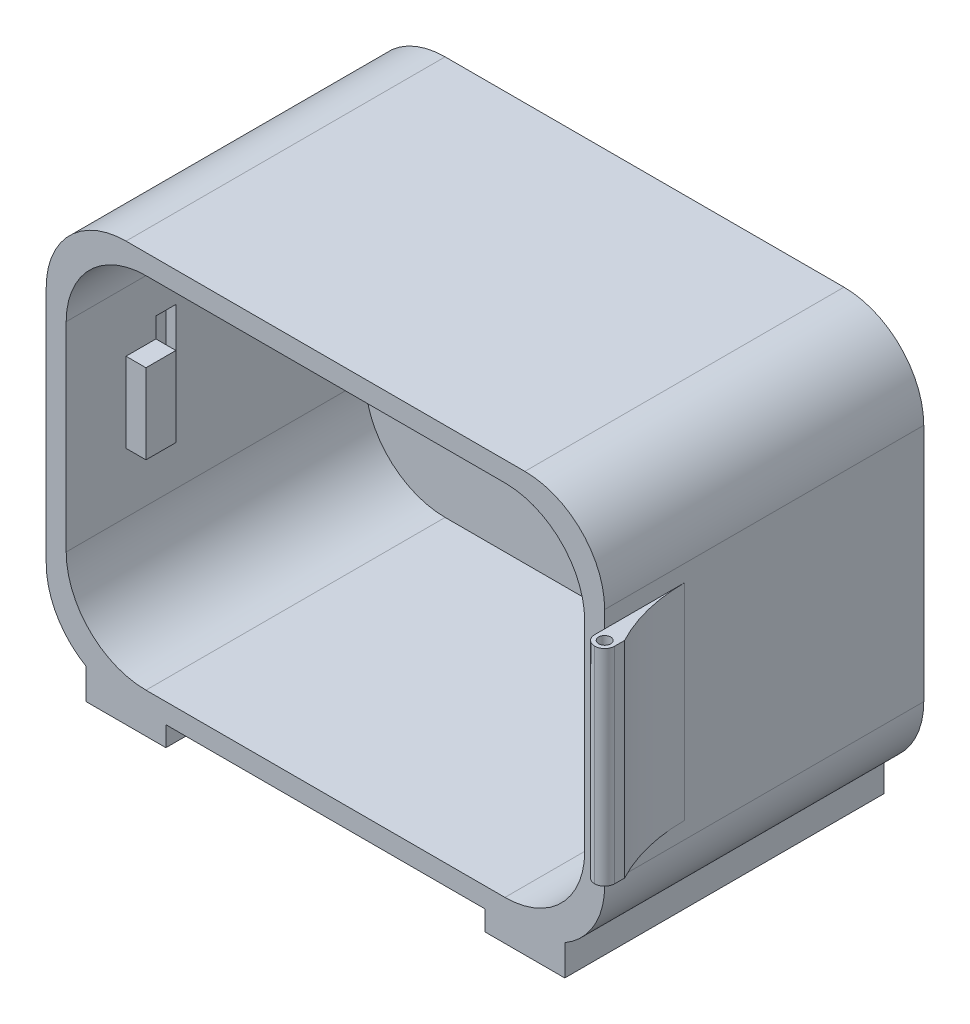
SolidWorks part; units mm, degrees
ref_plane "Front Plane" through (0, 0, 0) normal (0, 0, 1) x (1, 0, 0)
ref_plane "Top Plane" through (0, 0, 0) normal (0, 1, 0) x (1, 0, 0)
ref_plane "Right Plane" through (0, 0, 0) normal (1, 0, 0) x (0, 0, -1)
sketch "Sketch1" plane through (0, 0, 0) normal (0, 0, 1) x (1, 0, 0)
  line L0 (-82.55, 31.75) -> (-82.55, -31.75)
  line L1 (-63.5, 63.5) -> (63.5, 63.5)
  line L2 (-88.9, 38.1) -> (-88.9, -38.1)
  line L3 (-63.5, -63.5) -> (63.5, -63.5)
  line L4 (88.9, 38.1) -> (88.9, -38.1)
  line L5 (-88.9, 63.5) -> (88.9, -63.5) construction
  line L6 (-88.9, -63.5) -> (88.9, 63.5) construction
  line L7 (-57.15, -57.15) -> (57.15, -57.15)
  line L8 (82.55, 31.75) -> (82.55, -31.75)
  line L9 (-57.15, 57.15) -> (57.15, 57.15)
  line L10 (-88.9, 63.5) -> (88.9, 63.5) construction
  line L11 (88.9, 63.5) -> (88.9, -63.5) construction
  line L12 (82.55, 57.15) -> (82.55, -57.15) construction
  line L13 (-82.55, 57.15) -> (82.55, 57.15) construction
  line L14 (-82.55, -57.15) -> (82.55, -57.15) construction
  line L15 (-88.9, -63.5) -> (88.9, -63.5) construction
  line L16 (-82.55, 57.15) -> (-82.55, -57.15) construction
  line L17 (-88.9, 63.5) -> (-88.9, -63.5) construction
  arc A0 (63.5, 63.5) -> (88.9, 38.1) centre (63.5, 38.1) cw
  arc A1 (82.55, 31.75) -> (57.15, 57.15) centre (57.15, 31.75) ccw
  arc A2 (57.15, -57.15) -> (82.55, -31.75) centre (57.15, -31.75) ccw
  arc A3 (63.5, -63.5) -> (88.9, -38.1) centre (63.5, -38.1) ccw
  arc A4 (-82.55, -31.75) -> (-57.15, -57.15) centre (-57.15, -31.75) ccw
  arc A5 (-88.9, -38.1) -> (-63.5, -63.5) centre (-63.5, -38.1) ccw
  arc A6 (-63.5, 63.5) -> (-88.9, 38.1) centre (-63.5, 38.1) ccw
  arc A7 (-82.55, 31.75) -> (-57.15, 57.15) centre (-57.15, 31.75) cw
  point P0 (0, 0)
  dimension "D4" = 25.4
  dimension "D1" = 177.8
  dimension "D2" = 127
  dimension "D3" = 6.35
extrude "Boss-Extrude1" add sketch "Sketch1" against normal blind 95.25
sketch "Sketch2" plane through (0, 0, -95.25) normal (0, 0, -1) x (-1, 0, 0)
  line L0 (-63.5, 63.5) -> (63.5, 63.5)
  line L1 (-63.5, 63.5) -> (63.5, 63.5) construction
  line L2 (0, 63.5) -> (0, -63.5) construction
  line L3 (63.5, -63.5) -> (-63.5, -63.5) construction
  line L4 (63.5, -63.5) -> (-63.5, -63.5)
  line L5 (-88.9, -38.1) -> (-88.9, 38.1) construction
  line L6 (-88.9, -38.1) -> (-88.9, 38.1)
  line L7 (88.9, -38.1) -> (88.9, 38.1)
  arc A0 (-88.9, 38.1) -> (-63.5, 63.5) centre (-63.5, 38.1) cw
  arc A1 (-63.5, -63.5) -> (-88.9, -38.1) centre (-63.5, -38.1) cw
  arc A2 (-88.9, -38.1) -> (-63.5, -63.5) centre (-63.5, -38.1) ccw construction
  arc A3 (63.5, -63.5) -> (88.9, -38.1) centre (63.5, -38.1) ccw
  arc A4 (88.9, 38.1) -> (63.5, 63.5) centre (63.5, 38.1) ccw
extrude "Boss-Extrude2" add sketch "Sketch2" along normal blind 6.35
sketch "Sketch4" plane through (0, -63.5, 0) normal (0, -1, 0) x (1, 0, 0)
  line L0 (-76.2, 0) -> (-50.8, 0)
  line L2 (-76.2, 0) -> (-76.2, -101.6)
  line L3 (-88.9, -101.6) -> (-63.5, -101.6) construction
  line L4 (-76.2, -101.6) -> (-50.8, -101.6)
  line L5 (63.5, -101.6) -> (-63.5, -101.6) construction
  line L6 (-50.8, -101.6) -> (-50.8, 0)
  line L7 (0, 0) -> (0, -101.6) construction
  line L8 (-63.5, 0) -> (63.5, 0) construction
  line L9 (76.2, -101.6) -> (50.8, -101.6)
  line L10 (76.2, 0) -> (76.2, -101.6)
  line L11 (76.2, 0) -> (50.8, 0)
  line L12 (50.8, -101.6) -> (50.8, 0)
  point P4 (-63.5, 0)
  dimension "D1" = 25.4
extrude "Boss-Extrude3" add sketch "Sketch4" along normal blind 6.35 and the other way up to next
sketch "Sketch5" plane through (0, 0, 0) normal (0, 1, 0) x (1, 0, 0)
  line L0 (0, 0) -> (88.9, 0) construction
  line L1 (63.5, 0) -> (-63.5, 0) construction
  line L2 (92.075, 0) -> (95.25, 0) construction
  line L3 (88.9, 25.4) -> (88.9, 0)
  line L4 (92.075, 0) -> (92.075, -3.175) construction
  line L7 (95.25, -6.35) -> (88.9, -6.35)
  line L8 (95.25, -6.35) -> (95.25, 0)
  line L9 (95.25, 0) -> (92.075, 0)
  line L10 (88.9, -6.35) -> (88.9, 0)
  line L11 (95.25, -6.35) -> (88.9, 0) construction
  line L12 (95.25, 0) -> (88.9, -6.35) construction
  line L13 (88.9, -3.175) -> (95.25, -3.175) construction
  arc A3 (95.25, 0) -> (88.9, 25.4) centre (142.875, 25.4) cw
  circle A4 centre (92.075, -3.175) radius 1.905
  point P4 (93.6625, 0)
  dimension "D2" = 3.81
  dimension "D1" = 3.175
  dimension "D3" = 88.9
  dimension "D4" = 25.4
extrude "Boss-Extrude5" add sketch "Sketch5" along normal blind 32.766 and the other way blind 32.766 contours A3 L3 L10 L7 L8 A4 region at (91.243, 0, -2.9141)
fillet "Fillet1" radius 3.175 1 edges at (95.25, 0, 6.35)
sketch "Sketch6" plane through (0, 32.766, 0) normal (0, 1, 0) x (1, 0, 0)
  line L0 (90.17, -3.175) -> (88.9, -3.175) construction
  line L1 (88.9, 0) -> (88.9, -6.35) construction
  line L2 (93.98, -3.175) -> (95.25, -3.175) construction
  circle A0 centre (92.075, -3.175) radius 1.905 construction
sketch "Sketch8" plane through (-82.55, 0, 0) normal (1, 0, 0) x (0, 0, -1)
  line L0 (0, -19.05) -> (28.575, -19.05) construction
  line L1 (0, 31.75) -> (0, -31.75) construction
  line L2 (28.575, -19.05) -> (34.925, -19.05)
  line L3 (34.925, -19.05) -> (34.925, 19.05)
  line L4 (34.925, 19.05) -> (28.575, 19.05)
  line L5 (28.575, 19.05) -> (28.575, -19.05)
  line L6 (95.25, -57.15) -> (0, -57.15) construction
  dimension "D1" = 28.575
  dimension "D2" = 6.35
  dimension "D3" = 38.1
  dimension "D4" = 38.1
extrude "Cut-Extrude1" cut sketch "Sketch8" against normal blind 3.175
sketch "Sketch10" plane through (-82.55, 0, 0) normal (1, 0, 0) x (0, 0, -1)
  line L0 (28.575, 0) -> (28.575, 12.7) construction
  line L1 (28.575, 19.05) -> (28.575, -19.05) construction
  line L3 (28.575, 12.7) -> (19.05, 12.7)
  line L4 (28.575, 12.7) -> (28.575, -12.7)
  line L5 (28.575, -12.7) -> (19.05, -12.7)
  line L6 (19.05, 12.7) -> (19.05, -12.7)
  point P7 (28.575, 0)
  dimension "D1" = 12.7
  dimension "D2" = 9.525
extrude "Boss-Extrude6" add sketch "Sketch10" along normal blind 6.35
sketch "Sketch11" plane through (0, 0, -101.6) normal (0, 0, -1) x (-1, 0, 0)
  line L0 (32.462, -188.0741) -> (352.462, -188.0741) construction
  line L1 (-8.558, 38.2776) -> (9.4147, 38.2776)
  line L2 (9.4147, 38.2776) -> (12.3761, 30.5166)
  line L3 (12.3761, 30.5166) -> (6.5554, 30.5166)
  line L4 (-8.558, 38.2776) -> (-26.541, -14.1457)
  line L5 (-26.541, -14.1457) -> (-20.9531, -14.1457)
  line L6 (-20.9531, -17.5278) -> (-27.8644, -17.5278)
  line L7 (-27.8644, -17.5278) -> (-30.0702, -24.7333)
  line L8 (-30.0702, -24.7333) -> (-9.6303, -24.7333)
  line L9 (-9.6303, -24.7333) -> (-7.4245, -17.5278)
  line L10 (-7.4245, -17.5278) -> (8.4569, -17.5278)
  line L11 (8.4569, -17.5278) -> (10.5156, -24.7333)
  line L12 (10.5156, -24.7333) -> (12.3761, -24.7333)
  line L13 (12.3761, -24.7333) -> (12.3761, -18.8513)
  line L14 (16.1034, -18.8513) -> (16.1034, -24.7333)
  line L15 (16.1034, -24.7333) -> (21.2502, -24.7333)
  line L16 (21.2502, -24.7333) -> (21.2502, -18.8513)
  line L17 (24.3382, -18.8513) -> (24.3382, -24.7333)
  line L18 (24.3382, -24.7333) -> (31.2496, -24.7333)
  line L19 (31.2496, -24.7333) -> (13.3095, 27.1753)
  line L20 (13.3095, 27.1753) -> (6.5554, 27.1753)
  line L21 (0.7548, 15.0295) -> (-4.8523, -6.6891)
  line L22 (-4.8523, -6.6891) -> (6.0184, -6.6891)
  line L23 (6.0184, -6.6891) -> (0.7548, 15.0295)
  arc A0 (6.5554, 30.5166) -> (6.5554, 27.1753) centre (2.9252, 28.8459) ccw
  arc A1 (12.3761, -18.8513) -> (16.1034, -18.8513) centre (14.2398, -15.2135) cw
  arc A2 (-20.9531, -14.1457) -> (-20.9531, -17.5278) centre (-17.0513, -15.8368) cw
  arc A3 (21.2502, -18.8513) -> (24.3382, -18.8513) centre (22.7942, -15.1977) cw
  circle A4 centre (2.9252, 28.8459) radius 1.6706
  circle A5 centre (-17.0513, -15.8368) radius 2.045
  circle A6 centre (14.2398, -15.2135) radius 2.3144
  circle A7 centre (22.7942, -15.1977) radius 1.5563
  circle A8 centre (0, 3.175) radius 44.8241
  point P39 (0.8064, 15.13)
  point P41 (-4.8655, -6.7402)
  point P42 (6.0184, -6.6891)
  point P43 (0, 15.1186)
  point P44 (0.7548, 15.0295)
  point P45 (0, 0)
  point P46 (0, 2.7081)
  dimension "D1" = 3.175
extrude "Cut-Extrude4" cut sketch "Sketch11" against normal blind 1.5875 contours A8 | L22 L23 L21 | A3 L17 L18 L19 L20 A0 L3 L2 L1 L4 L5 A2 L6 L7 L8 L9 L10 L11 L12 L13 A1 L14 L15 L16
sketch "Sketch12" plane through (0, 0, -101.6) normal (0, 0, -1) x (-1, 0, 0)
  line L0 (0, 0) -> (0, -57.15) construction
  line L1 (63.5, -57.15) -> (-63.5, -57.15) construction
  text T0 "amp-lab.org" font "Century Gothic" height in points 48
  point P6 (0, -57.15)
  dimension "D1" = 57.15
  dimension "D2" = 127
extrude "Cut-Extrude5" cut sketch "Sketch12" against normal blind 1.5875
fillet "Fillet2" radius 3.175 1 edges at (88.9, 0, 6.35)
